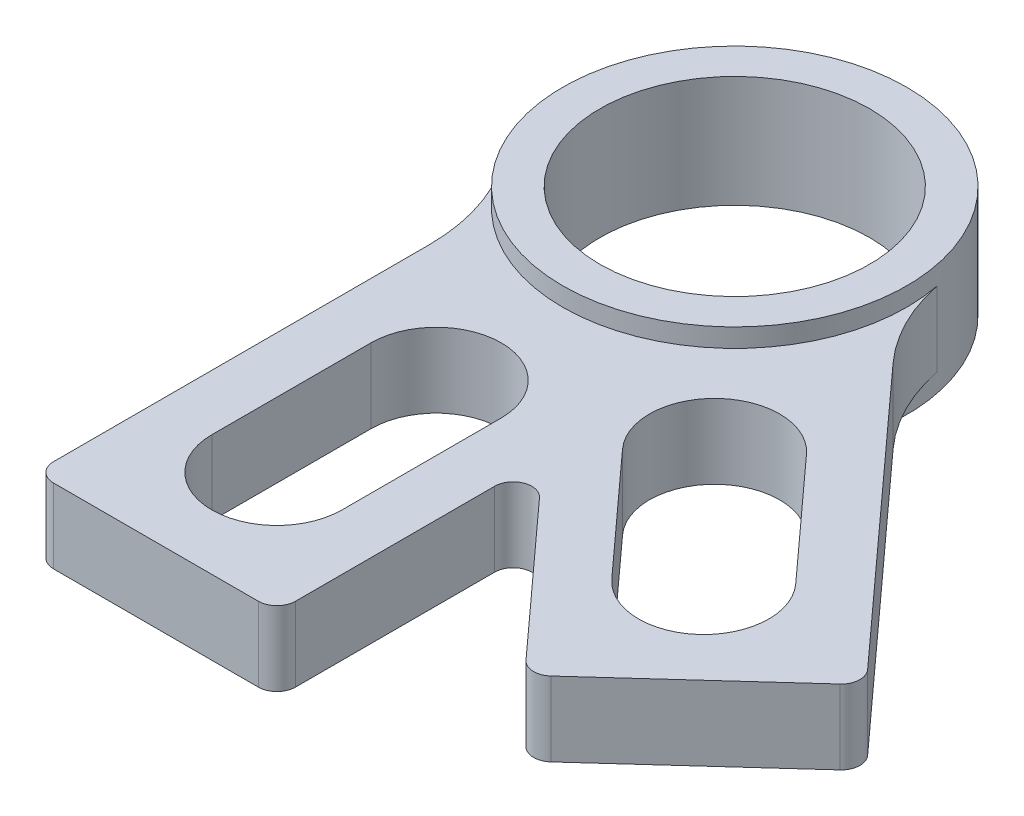
SolidWorks part; units mm, degrees
material "AISI 4130 Steel, annealed at 865C"
ref_plane "Front Plane" through (0, 0, 0) normal (0, 0, 1) x (1, 0, 0)
ref_plane "Top Plane" through (0, 0, 0) normal (0, 1, 0) x (1, 0, 0)
ref_plane "Right Plane" through (0, 0, 0) normal (1, 0, 0) x (0, 0, -1)
sketch "Sketch1" plane through (0, 0, 0) normal (0, 1, 0) x (1, 0, 0)
  line L0 (0, 0) -> (0, -49.3903) construction
  line L1 (0, 0) -> (33.2105, -36.5577) construction
  line L2 (0, -39.0716) -> (0, -25.4826) construction
  line L3 (-5.5562, -39.0716) -> (-5.5562, -25.4826)
  line L4 (5.5563, -39.0716) -> (5.5563, -25.4826)
  line L5 (26.2721, -28.92) -> (17.1347, -18.8617) construction
  line L6 (22.1594, -32.656) -> (13.0221, -22.5977)
  line L7 (30.3847, -25.1839) -> (21.2473, -15.1256)
  line L8 (0, -49.3903) -> (0, -44.6278) construction
  line L9 (33.2105, -36.5577) -> (30.0081, -33.0326) construction
  line L10 (-10.3187, -49.3903) -> (10.3188, -49.3903)
  line L11 (25.5728, -43.4961) -> (40.8482, -29.6193)
  line L12 (-10.3187, -49.3903) -> (-10.3187, -10.4432)
  line L13 (10.3188, -49.3903) -> (10.3188, -26.7047)
  line L14 (40.8482, -29.6193) -> (14.6599, -0.7914)
  line L15 (25.5728, -43.4961) -> (10.3188, -26.7047)
  line L16 (195.717, -215.4428) -> (13.8127, -15.2048) construction
  line L22 (0, 0) -> (10.3188, -26.7047) construction
  circle A0 centre (0, 0) radius 11.5062
  circle A1 centre (0, 0) radius 14.6812
  arc A2 (-5.5562, -39.0716) -> (5.5563, -39.0716) centre (0, -39.0716) ccw
  arc A3 (5.5563, -25.4826) -> (-5.5562, -25.4826) centre (0, -25.4826) ccw
  arc A4 (22.1594, -32.656) -> (30.3847, -25.1839) centre (26.2721, -28.92) ccw
  arc A5 (21.2473, -15.1256) -> (13.0221, -22.5977) centre (17.1347, -18.8617) ccw
  point P8 (0, -32.2771)
  point P13 (21.7034, -23.8908)
  point P25 (0, -49.3903)
  point P27 (33.2105, -36.5577)
  dimension "D2" = 29.3624
  dimension "D3" = 4.7625
  dimension "D4" = 4.7625
  dimension "D5" = 13.589
  dimension "D6" = 49.3903
  dimension "D7" = 20.6375
extrude "Bearing_Insert_Extrude" add sketch "Sketch1" along normal mid plane 9.525 contours A1 A0 region at (-5.4988, 0, -13.1636)
extrude "Apex_Slot_Insert_Extrude" add sketch "Sketch1<4>" along normal mid plane 6.35 contours A1 L12 L10 L13 L15 L11 L14 A5 L7 A4 L6 A3 L4 A2 L3 region at (-9.6131, 0, 29.9168)
sketch "Sketch1<4>" plane through (0, 0, 0) normal (0, 1, 0) x (1, 0, 0) same geometry as "Sketch1"
fillet "Fillet1" radius 16.002 2 edges at (14.6599, 0, 0.7914) (-10.3187, 0, 10.4432)
fillet "Fillet2" radius 1.5875 5 edges at (40.8482, 0, 29.6193) (25.5728, 0, 43.4961) (10.3188, 0, 26.7047) (10.3188, 0, 49.3903) (-10.3187, 0, 49.3903)
equation "\"Apex_thickness\"= .25"
equation "\"Bearing_diameter\"= 0.906in"
equation "\"A-arm_angle\"= 39.1893"
equation "\"D1@Sketch1\"=\"Bearing_diameter\""
equation "\"D1@Apex_Slot_Insert_Extrude\"=\"Apex_thickness\""
